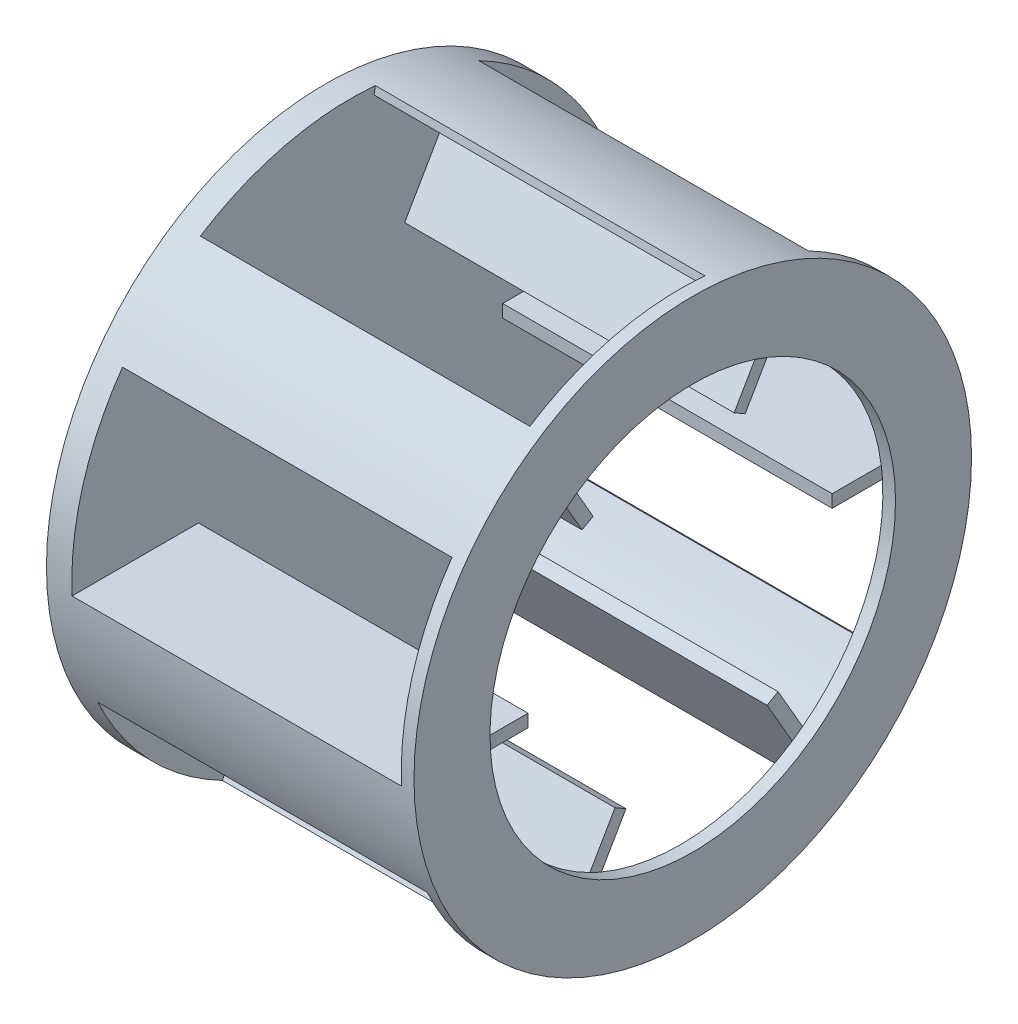
SolidWorks part; units mm, degrees
ref_plane "Front Plane" through (0, 0, 0) normal (0, 0, 1) x (1, 0, 0)
ref_plane "Top Plane" through (0, 0, 0) normal (0, 1, 0) x (1, 0, 0)
ref_plane "Right Plane" through (0, 0, 0) normal (1, 0, 0) x (0, 0, -1)
sketch "Sketch3" plane through (0, 0, 0) normal (1, 0, 0) x (0, 0, -1)
  line L0 (0, 0) -> (0, 161779.3831) construction
  line L1 (0, 0) -> (161779.3831, 0) construction
  circle A0 centre (0, 0) radius 19.05
  circle A1 centre (0, 0) radius 38.1
  circle A2 centre (0, 0) radius 139.7
  dimension "D1" = 279.4
  dimension "D2" = 76.2
  dimension "1.5" = 38.1
extrude "Boss-Extrude1" add sketch "Sketch3" against normal blind 76.2 contours A1 A0 region at (0, 0, 37.0224)
extrude "Boss-Extrude2" add sketch "Sketch3<3>" against normal blind 12.7 contours A2 A1 region at (0, 0, 135.7487)
sketch "Sketch3<3>" plane through (0, 0, 0) normal (1, 0, 0) x (0, 0, -1) same geometry as "Sketch3"
sketch "Sketch4" plane through (0, 0, 0) normal (1, 0, 0) x (0, 0, -1)
  line L0 (0, 0) -> (0, 50000) construction
  line L1 (0, 2.2513) -> (0, -49997.7487) construction
  line L2 (0, 0) -> (50000, 0) construction
  line L3 (-69.85, 120.9837) -> (0, 0)
  line L4 (0, 0) -> (-24.2587, 137.5776)
  line L5 (-75.3493, 117.8087) -> (-5.4993, -3.175)
  line L6 (-43.5993, 62.8161) -> (-38.1, 65.9911)
  line L7 (-80.8485, 114.6337) -> (-10.9985, -6.35)
  line L8 (-10.9985, -6.35) -> (-118.0149, 83.4474)
  line L9 (-43.5993, 62.8161) -> (-49.0985, 59.6411)
  circle A1 centre (0, 0) radius 139.7 construction
  circle A4 centre (0, 0) radius 135.89
  circle A5 centre (0, 0) radius 135.89
  circle M8 centre (0, 0) radius 139.7
  dimension "D1" = 60
  dimension "D2" = 20
  dimension "D5" = 63.5
  dimension "D3" = 6.35
  dimension "D4" = 3.81
extrude "Boss-Extrude3" [suppressed] add sketch "Sketch4" along normal blind 165.1 contours A5 L4 L3 M8 | A5 L3 L5 M8 | L3 A5 L5 L6
extrude "Boss-Extrude5" add sketch "Sketch4<4>" along normal blind 165.1 contours L5 A5 L7 L9 | A5 L7 L8 M8 | A5 L5 L7 M8 region at (0, 86.9272, 61.1813) region at (0, 114.2744, 76.9768) region at (0, 96.7469, 97.1802)
sketch "Sketch4<4>" plane through (0, 0, 0) normal (1, 0, 0) x (0, 0, -1) same geometry as "Sketch4"
pattern_circular "CirPattern1" count 6 over 360 about axis through (0, 0, 0) along (1, 0, 0) of "Boss-Extrude5"
sketch "Sketch5" plane through (165.1, 0, 0) normal (1, 0, 0) x (0, 0, -1)
  circle A0 centre (0, 0) radius 139.7
  circle A1 centre (0, 0) radius 101.6
  arc A2 (126.7135, 58.8199) -> (64.2785, 124.0337) centre (0, 0) ccw construction
  point P5 (0, 0)
  dimension "D1" = 203.2
extrude "Boss-Extrude6" add sketch "Sketch5" along normal blind 6.35
